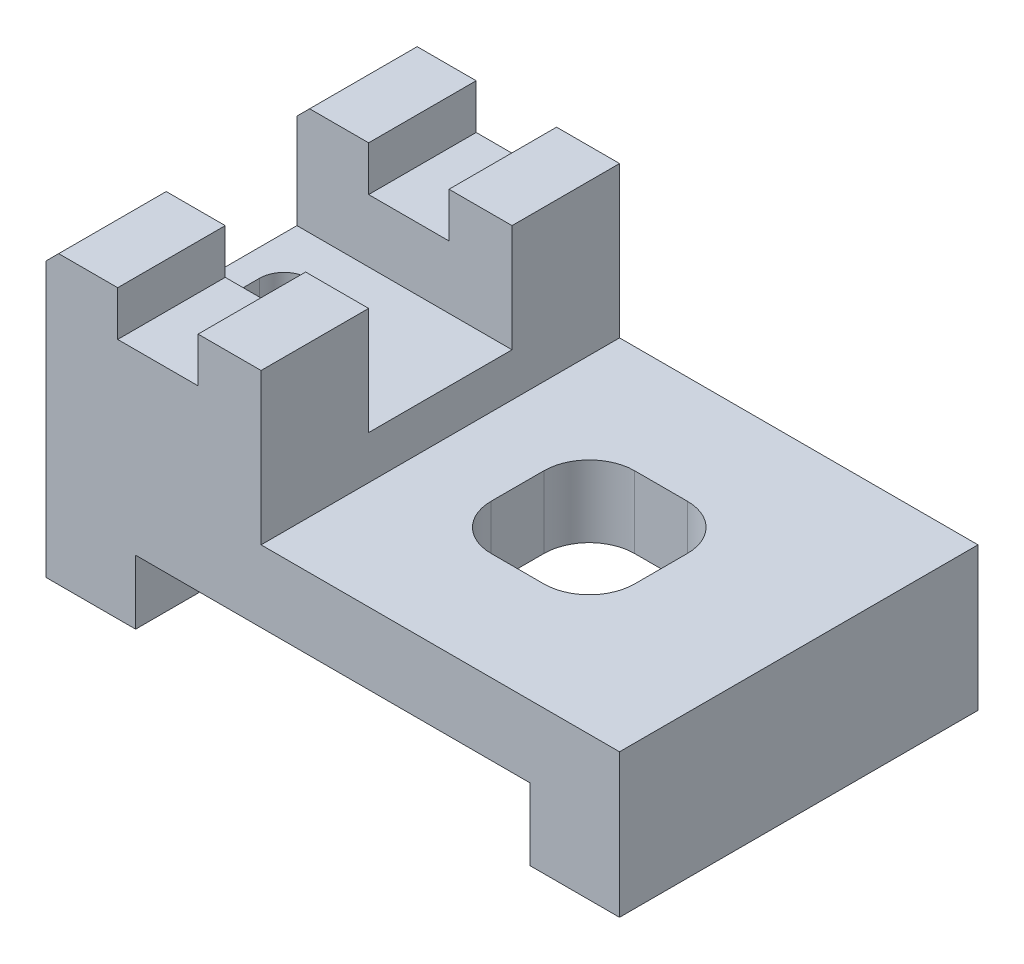
SolidWorks part; units mm, degrees
ref_plane "Front Plane" through (0, 0, 0) normal (0, 0, 1) x (1, 0, 0)
ref_plane "Top Plane" through (0, 0, 0) normal (0, 1, 0) x (1, 0, 0)
ref_plane "Right Plane" through (0, 0, 0) normal (1, 0, 0) x (0, 0, -1)
sketch "Sketch1" plane through (0, 0, 0) normal (0, 0, 1) x (1, 0, 0)
  line L0 (-30.3581, 24.5019) -> (-30.3581, -24.053)
  line L1 (-30.3581, -24.053) -> (-14.4831, -24.053)
  line L2 (-14.4831, -24.053) -> (-14.4831, -12.7)
  line L3 (-14.4831, -12.7) -> (55.3579, -12.7)
  line L4 (55.3579, -12.7) -> (55.3579, -25.4)
  line L5 (55.3579, -25.4) -> (71.2329, -25.4)
  line L6 (71.2329, -25.4) -> (71.2329, 0)
  line L7 (71.2329, 0) -> (7.7419, 0)
  line L8 (7.7419, 0) -> (7.7419, 26.747)
  line L9 (7.7419, 26.747) -> (-3.4187, 26.747)
  line L10 (-3.4187, 26.747) -> (-3.4187, 18.8095)
  line L11 (-3.4187, 18.8095) -> (-17.6581, 18.8095)
  line L12 (-17.6581, 18.8095) -> (-17.6581, 26.747)
  line L13 (-17.6581, 26.747) -> (-28.1131, 26.747)
  line L14 (-28.1131, 26.747) -> (-30.3581, 24.5019)
  point P12 (20.4374, -12.7)
  point P18 (-20.878, -37.186)
  point P19 (-70.8986, 11.3415)
  dimension "D1" = 50.8
  dimension "D2" = 7.9375
  dimension "D3" = 3.175
  dimension "D4" = 15.875
  dimension "D5" = 101.6
  dimension "D6" = 15.875
  dimension "D7" = 12.7
  dimension "D8" = 25.4
  dimension "D9" = 38.1
  dimension "D10" = 12.7
  dimension "D11" = 45
extrude "Boss-Extrude1" add sketch "Sketch1" along normal blind 63.5
sketch "Sketch5" plane through (0, 26.747, 0) normal (0, 1, 0) x (1, 0, 0)
  line L0 (-17.6581, -63.5) -> (-28.1131, -63.5) construction
  line L2 (-17.6581, -63.5) -> (-17.6581, 0) construction
  line L7 (-4.9581, -19.8754) -> (-30.3581, -43.6246) construction
  line L8 (-4.9581, -43.6246) -> (-30.3581, -19.8754) construction
  line L9 (-30.3581, -63.5) -> (-30.3581, 0) construction
  line L11 (7.7419, -19.05) -> (-30.3581, -19.05)
  line L12 (7.7419, -19.05) -> (7.7419, -44.45)
  line L13 (7.7419, -44.45) -> (-30.3581, -44.45)
  line L14 (-30.3581, -19.05) -> (-30.3581, -44.45)
  line L15 (7.7419, -19.05) -> (-30.3581, -44.45) construction
  line L16 (7.7419, -44.45) -> (-30.3581, -19.05) construction
  point P6 (-17.6581, -31.75)
  point P15 (-11.3081, -31.75)
  dimension "D1" = 38.1
  dimension "D2" = 25.4
  dimension "D3" = 19.05
extrude "Cut-Extrude1" cut sketch "Sketch5" against normal blind 19.05
sketch "Sketch6" plane through (0, 0, 0) normal (0, 1, 0) x (1, 0, 0)
  line L0 (71.2329, -63.5) -> (7.7419, -63.5) construction
  line L1 (29.4591, -19.05) -> (38.7868, -19.05)
  line L2 (21.4229, -27.0861) -> (21.4229, -36.4139)
  line L3 (29.4591, -44.45) -> (38.7868, -44.45)
  line L4 (46.8229, -27.0861) -> (46.8229, -36.4139)
  line L5 (21.4229, -19.05) -> (46.8229, -44.45) construction
  line L6 (21.4229, -44.45) -> (46.8229, -19.05) construction
  arc A0 (46.8229, -27.0861) -> (38.7868, -19.05) centre (38.7868, -27.0861) ccw
  arc A1 (38.7868, -44.45) -> (46.8229, -36.4139) centre (38.7868, -36.4139) ccw
  arc A2 (29.4591, -44.45) -> (21.4229, -36.4139) centre (29.4591, -36.4139) cw
  arc A3 (29.4591, -19.05) -> (21.4229, -27.0861) centre (29.4591, -27.0861) ccw
  point P0 (34.1229, -31.75)
  dimension "D4" = 8.0361
  dimension "D1" = 25.4
  dimension "D2" = 19.05
  dimension "D3" = 25.4
extrude "Cut-Extrude2" cut sketch "Sketch6" against normal up to surface (12.7 mm away) up to face at (20.4374, -12.7, 31.75)
sketch "Sketch7" plane through (0, 7.697, 0) normal (0, 1, 0) x (1, 0, 0)
  line L0 (-30.3581, -19.05) -> (-30.3581, -44.45) construction
  line L1 (-21.2866, -26.1116) -> (-14.0297, -26.1116)
  line L2 (-25.5956, -30.4207) -> (-25.5956, -33.0793)
  line L3 (-21.2866, -37.3884) -> (-14.0297, -37.3884)
  line L4 (-9.7206, -30.4207) -> (-9.7206, -33.0793)
  line L5 (-25.5956, -26.1116) -> (-9.7206, -37.3884) construction
  line L6 (-25.5956, -37.3884) -> (-9.7206, -26.1116) construction
  arc A0 (-14.0297, -37.3884) -> (-9.7206, -33.0793) centre (-14.0297, -33.0793) ccw
  arc A1 (-25.5956, -30.4207) -> (-21.2866, -26.1116) centre (-21.2866, -30.4207) cw
  arc A2 (-9.7206, -30.4207) -> (-14.0297, -26.1116) centre (-14.0297, -30.4207) ccw
  arc A3 (-21.2866, -37.3884) -> (-25.5956, -33.0793) centre (-21.2866, -33.0793) cw
  point P0 (-17.6581, -31.75)
  dimension "D3" = 4.3091
  dimension "D1" = 15.875
  dimension "D2" = 4.7625
extrude "Cut-Extrude3" cut sketch "Sketch7" against normal blind 13.97
